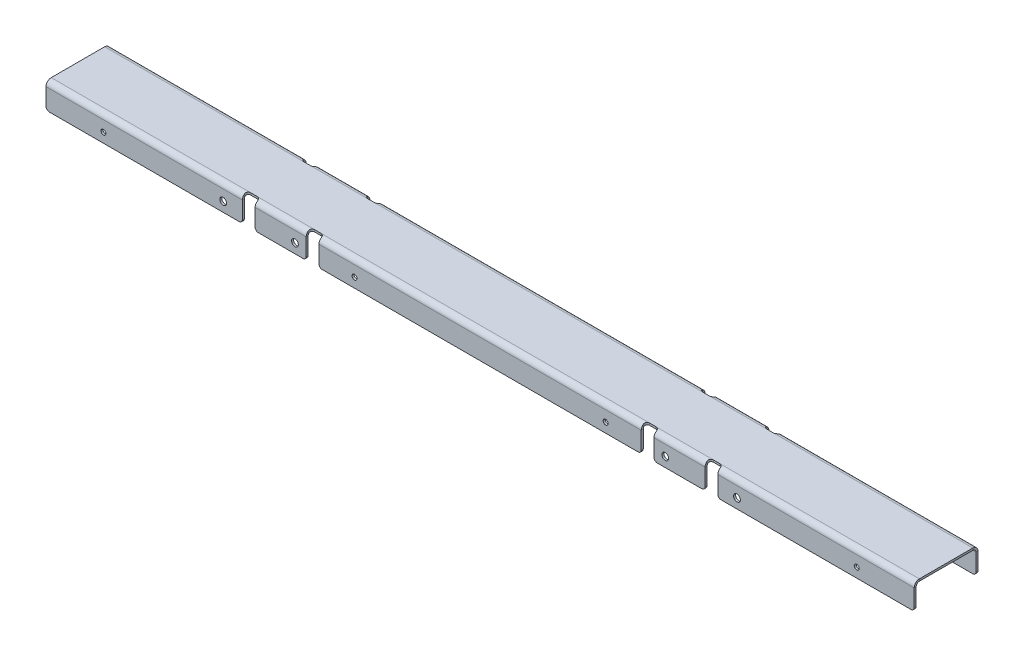
SolidWorks part; units mm, degrees
note: The reader was unsure of these and kept them because the rebuilt part matched: thickness of "Base-Flange1", "Edge-Flange1", "Sheet-Metal1", "Sheet-Metal4", "Sheet-Metal5", "Sheet-Metal6", "Sheet-Metal7"; flange length of "Edge-Flange1".
material "5052-H32"
ref_plane "Front Plane" through (0, 0, 0) normal (0, 0, 1) x (1, 0, 0)
ref_plane "Top Plane" through (0, 0, 0) normal (0, 1, 0) x (1, 0, 0)
ref_plane "Right Plane" through (0, 0, 0) normal (1, 0, 0) x (0, 0, -1)
sketch "Sketch1" plane through (0, 0, 0) normal (0, 1, 0) x (1, 0, 0)
  line L1 (0, 0) -> (863.6, 0)
  line L2 (0, 0) -> (0, 63.5)
  line L3 (0, 63.5) -> (863.6, 63.5)
  line L4 (863.6, 0) -> (863.6, 63.5)
  dimension "D1" = 63.5
  dimension "D2" = 863.6
base flange "Base-Flange1" sketch "Sketch1" thickness 2.032 reverse thickness direction no parameters "D1"=3.175
edge flange "Edge-Flange1" sketch "Sketch6" flange profiles "Sketch6", "Sketch7" flange angle 90 flange length 25.4 flange position material inside bend radius 3.175 thickness 2.032 parameters "D6"=10, "D8"=1
sketch "Sketch6" plane through (0, -2.032, 0) normal (0, 0, 1) x (-1, 0, 0)
  line L0 (0, 0) -> (-863.6, 0) construction
  line L1 (0, 0) -> (-863.6, 0)
  line L2 (-863.6, 0) -> (-863.6, 23.368)
  line L3 (-863.6, 23.368) -> (0, 23.368)
  line L4 (0, 23.368) -> (0, 0)
sketch "Sketch7" plane through (0, -2.032, -63.5) normal (0, 0, -1) x (1, 0, 0)
  line L0 (863.6, 0) -> (0, 0) construction
  line L1 (863.6, 0) -> (0, 0)
  line L2 (0, 0) -> (0, 23.368)
  line L3 (0, 23.368) -> (863.6, 23.368)
  line L4 (863.6, 23.368) -> (863.6, 0)
bend "EdgeBend1" bend radius 3.175 bend angle 90 parameters "D5"=1
bend "EdgeBend2" bend radius 3.175 bend angle 90 parameters "D5"=2
sketch "Sketch8" plane through (0, 0, -63.5) normal (0, 0, -1) x (-1, 0, 0)
  line L0 (-863.6, -5.207) -> (-863.6, -25.4) construction
  line L1 (-863.6, -25.4) -> (0, -25.4) construction
  line L2 (0, -25.4) -> (0, -5.207) construction
  line L3 (-431.8, -25.4) -> (-431.8, 0) construction
  line L4 (-863.6, 0) -> (0, 0) construction
  circle A0 centre (-806.45, -15.875) radius 2.4575
  circle A1 centre (-556.6833, -15.875) radius 2.4575
  circle A2 centre (-306.9167, -15.875) radius 2.4575
  circle A3 centre (-57.15, -15.875) radius 2.4575
  circle A4 centre (-687.3392, -15.875) radius 3.3734
  circle A5 centre (-615.9652, -15.875) radius 3.3734
  circle A6 centre (-247.6348, -15.875) radius 3.3734
  circle A7 centre (-176.2608, -15.875) radius 3.3734
  dimension "D2" = 9.525
  dimension "D3" = 4.9149
  dimension "D7" = 6.7469
  dimension "D10" = 6.7469
  dimension "D1" = 57.15
  dimension "D5" = 57.15
  dimension "D6" = 176.2608
  dimension "D8" = 9.525
  dimension "D9" = 71.374
  dimension "D11" = 9.525
  dimension "D12" = 431.8
  dimension "D4" = 4
extrude "Cut-Extrude1" cut sketch "Sketch8" against normal through all
sketch "Sketch9" plane through (0, 0, -63.5) normal (0, 0, -1) x (-1, 0, 0)
  line L0 (-863.6, -25.4) -> (0, -25.4) construction
  line L1 (-668.2892, -25.4) -> (-655.5892, -25.4)
  line L2 (-668.2892, -25.4) -> (-668.2892, 0)
  line L3 (-668.2892, 0) -> (-655.5892, 0)
  line L4 (-655.5892, -25.4) -> (-655.5892, 0)
  line L5 (-863.6, 0) -> (0, 0) construction
  line L7 (-604.7892, 0) -> (-592.0892, 0)
  line L8 (-604.7892, 0) -> (-604.7892, -25.4)
  line L9 (-604.7892, -25.4) -> (-592.0892, -25.4)
  line L10 (-592.0892, 0) -> (-592.0892, -25.4)
  line L11 (-195.3108, 0) -> (-208.0108, 0)
  line L12 (-195.3108, 0) -> (-195.3108, -25.4)
  line L13 (-195.3108, -25.4) -> (-208.0108, -25.4)
  line L14 (-208.0108, 0) -> (-208.0108, -25.4)
  line L15 (-258.8108, 0) -> (-271.5108, 0)
  line L16 (-258.8108, 0) -> (-258.8108, -25.4)
  line L17 (-258.8108, -25.4) -> (-271.5108, -25.4)
  line L18 (-271.5108, 0) -> (-271.5108, -25.4)
  circle A0 centre (-687.3392, -15.875) radius 3.3734 construction
  circle A1 centre (-176.2608, -15.875) radius 3.3734 construction
  dimension "D1" = 12.7
  dimension "D2" = 19.05
  dimension "D3" = 12.7
  dimension "D4" = 63.5
  dimension "D5" = 12.7
  dimension "D6" = 12.7
  dimension "D7" = 19.05
  dimension "D8" = 63.5
extrude "Cut-Extrude2" cut sketch "Sketch9" against normal up to vertex
ref_plane "Plane1" through (0, 0, -31.75) normal (0, 0, -1) x (-1, 0, 0)
mirror "Mirror1" about plane through (0, 0, -31.75) normal (0, 0, -1) of "Cut-Extrude2"
fillet "Fillet1" radius 3.175 36 edges at (0, -25.4, -1.016) (0, -25.4, -62.484) (863.6, -25.4, -1.016) (863.6, -25.4, -62.484) (258.8108, -1.016, -58.293) (271.5108, -1.016, -58.293) (208.0108, -1.016, -58.293) (195.3108, -1.016, -58.293) (258.8108, -1.016, -5.207) (195.3108, -1.016, -5.207) (195.3108, -25.4, -1.016) (195.3108, -25.4, -62.484) (208.0108, -25.4, -62.484) (208.0108, -1.016, -5.207) (208.0108, -25.4, -1.016) (258.8108, -25.4, -62.484) (271.5108, -25.4, -62.484) (258.8108, -25.4, -1.016) (271.5108, -25.4, -1.016) (271.5108, -1.016, -5.207) (604.7892, -1.016, -5.207) (668.2892, -1.016, -5.207) (655.5892, -1.016, -5.207) (592.0892, -1.016, -5.207) (592.0892, -25.4, -1.016) (604.7892, -25.4, -1.016) (668.2892, -25.4, -1.016) (655.5892, -25.4, -1.016) (592.0892, -1.016, -58.293) (592.0892, -25.4, -62.484) (604.7892, -25.4, -62.484) (604.7892, -1.016, -58.293) (668.2892, -25.4, -62.484) (668.2892, -1.016, -58.293) (655.5892, -25.4, -62.484) (655.5892, -1.016, -58.293)
sketch "Bend-Lines1" [suppressed] plane through (0, 0, 0) normal (0, 1, 0) x (1, 0, 0)
sketch "Bounding-Box1" [suppressed] plane through (0, 0, 0) normal (0, 1, 0) x (1, 0, 0)
sheet metal parameters "Sheet-Metal1" thickness 2.032 parameters "D1"=3.175
flat pattern "Flat-Pattern1" [suppressed]
sketch "Bend-Lines2" plane through (0, 0, 0) normal (0, 1, 0) x (1, 0, 0)
sketch3d "Bounding-Box2" [suppressed]
  line L0 (863.6, 63.5, 0) -> (0, 63.5, 0) construction
  line L1 (863.6, 0, 0) -> (0, 0, 0) construction
  line L2 (863.6, 63.5, 0) -> (863.6, 0, 0) construction
  line L3 (0, 63.5, 0) -> (0, 0, 0) construction
sheet metal parameters "Sheet-Metal4" thickness 2.032 parameters "D1"=3.175, "D7"=3.175
flat pattern "Flat-Pattern1"
sketch "Bend-Lines2" plane through (0, 0, 0) normal (0, 1, 0) x (1, 0, 0)
  line L0 (863.6, 60.8905) -> (0, 60.8905) construction
  line L1 (0, 2.6095) -> (863.6, 2.6095) construction
  line L2 (863.6, 60.8905) -> (0, 60.8905) construction
  line L3 (0, 2.6095) -> (863.6, 2.6095) construction
sketch3d "Bounding-Box2" [suppressed]
  line L0 (863.6, 83.6809, 0) -> (0, 83.6809, 0) construction
  line L1 (863.6, -20.1809, 0) -> (0, -20.1809, 0) construction
  line L2 (863.6, 83.6809, 0) -> (863.6, -20.1809, 0) construction
  line L3 (0, 83.6809, 0) -> (0, -20.1809, 0) construction
bend of the flat pattern "Flatten-<EdgeBend1>1"
bend of the flat pattern "Flatten-<EdgeBend2>1"
sheet metal parameters "Sheet-Metal5" thickness 2.032 parameters "D1"=3.175, "D7"=3.175
flat pattern "Flat-Pattern1"
sketch "Bend-Lines2" plane through (0, 0, 0) normal (0, 1, 0) x (1, 0, 0)
  line L0 (863.6, 61.5846) -> (0, 61.5846) construction
  line L1 (0, 1.9154) -> (863.6, 1.9154) construction
  line L2 (863.6, 61.5846) -> (0, 61.5846) construction
  line L3 (0, 1.9154) -> (863.6, 1.9154) construction
sketch3d "Bounding-Box2" [suppressed]
  line L0 (863.6, 85.0692, 0) -> (0, 85.0692, 0) construction
  line L1 (863.6, -21.5692, 0) -> (0, -21.5692, 0) construction
  line L2 (863.6, 85.0692, 0) -> (863.6, -21.5692, 0) construction
  line L3 (0, 85.0692, 0) -> (0, -21.5692, 0) construction
bend of the flat pattern "Flatten-<EdgeBend1>1"
bend of the flat pattern "Flatten-<EdgeBend2>1"
sheet metal parameters "Sheet-Metal6" thickness 2.032 parameters "D1"=3.175, "D7"=3.175
flat pattern "Flat-Pattern1"
sketch "Bend-Lines2" plane through (0, 0, 0) normal (0, 1, 0) x (1, 0, 0)
  line L0 (863.6, 61.5846) -> (668.2892, 61.5846) construction
  line L1 (0, 1.9154) -> (863.6, 1.9154) construction
  line L2 (863.6, 61.5846) -> (668.2892, 61.5846) construction
  line L3 (0, 1.9154) -> (863.6, 1.9154) construction
  line L4 (655.5892, 61.5846) -> (604.7892, 61.5846) construction
  line L5 (592.0892, 61.5846) -> (271.5108, 61.5846) construction
  line L6 (258.8108, 61.5846) -> (208.0108, 61.5846) construction
  line L7 (195.3108, 61.5846) -> (0, 61.5846) construction
sketch3d "Bounding-Box2" [suppressed]
  line L0 (863.6, 85.0692, 0) -> (0, 85.0692, 0) construction
  line L1 (863.6, -21.5692, 0) -> (0, -21.5692, 0) construction
  line L2 (863.6, 85.0692, 0) -> (863.6, -21.5692, 0) construction
  line L3 (0, 85.0692, 0) -> (0, -21.5692, 0) construction
bend of the flat pattern "Flatten-<EdgeBend1>1"
bend of the flat pattern "Flatten-<EdgeBend2>1"
sheet metal parameters "Sheet-Metal7" thickness 2.032 parameters "D1"=3.175, "D7"=3.175
flat pattern "Flat-Pattern1"
sketch "Bend-Lines2" plane through (0, 0, 0) normal (0, 1, 0) x (1, 0, 0)
  line L0 (863.6, 61.5846) -> (668.2892, 61.5846) construction
  line L1 (0, 1.9154) -> (195.3108, 1.9154) construction
  line L2 (863.6, 61.5846) -> (668.2892, 61.5846) construction
  line L3 (0, 1.9154) -> (195.3108, 1.9154) construction
  line L4 (655.5892, 61.5846) -> (604.7892, 61.5846) construction
  line L5 (592.0892, 61.5846) -> (271.5108, 61.5846) construction
  line L6 (258.8108, 61.5846) -> (208.0108, 61.5846) construction
  line L7 (195.3108, 61.5846) -> (0, 61.5846) construction
  line L8 (208.0108, 1.9154) -> (258.8108, 1.9154) construction
  line L9 (271.5108, 1.9154) -> (592.0892, 1.9154) construction
  line L10 (604.7892, 1.9154) -> (655.5892, 1.9154) construction
  line L11 (668.2892, 1.9154) -> (863.6, 1.9154) construction
sketch3d "Bounding-Box2" [suppressed]
  line L0 (863.6, 85.0692, 0) -> (0, 85.0692, 0) construction
  line L1 (863.6, -21.5692, 0) -> (0, -21.5692, 0) construction
  line L2 (863.6, 85.0692, 0) -> (863.6, -21.5692, 0) construction
  line L3 (0, 85.0692, 0) -> (0, -21.5692, 0) construction
bend of the flat pattern "Flatten-<EdgeBend1>1"
bend of the flat pattern "Flatten-<EdgeBend2>1"
